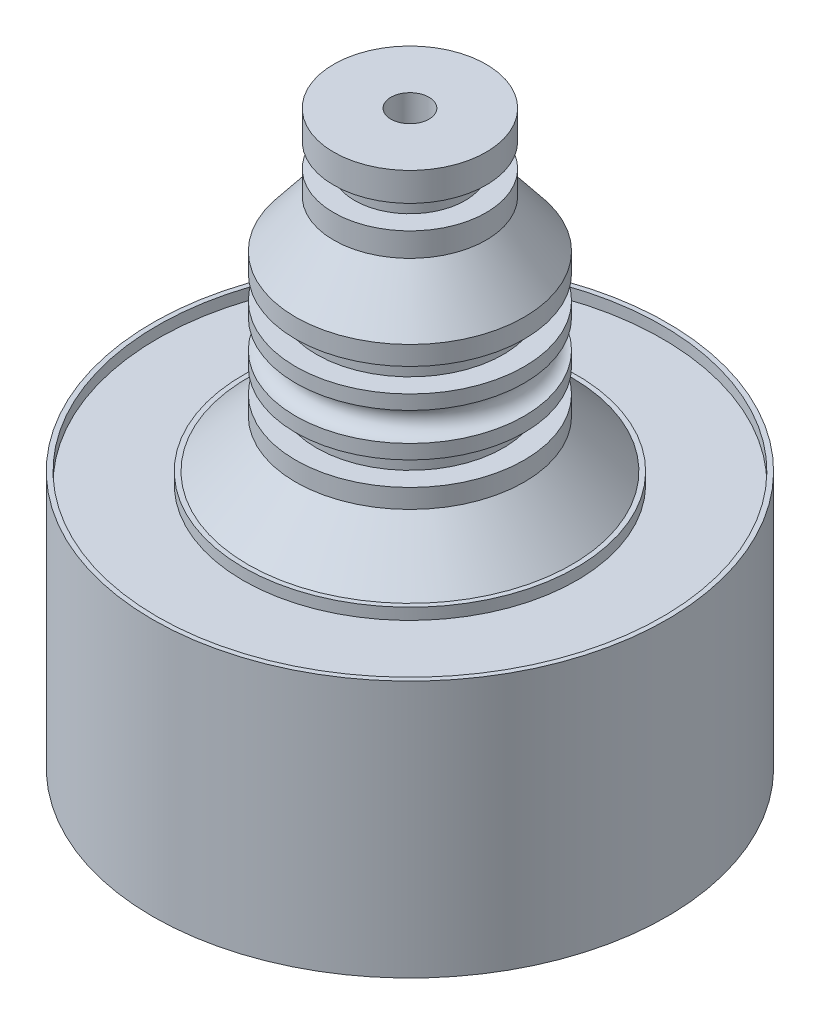
SolidWorks part; units mm, degrees
ref_plane "Спереди" through (0, 0, 0) normal (0, 0, 1) x (1, 0, 0)
ref_plane "Сверху" through (0, 0, 0) normal (0, 1, 0) x (1, 0, 0)
ref_plane "Справа" through (0, 0, 0) normal (1, 0, 0) x (0, 0, -1)
sketch "Эскиз1" plane through (0, 0, 0) normal (0, 0, 1) x (1, 0, 0)
  line L0 (0, 0) -> (0, 60) construction
  line L1 (-25, 0) -> (25, 0) construction
  line L2 (2, 60) -> (2, 0)
  line L4 (2, 60) -> (8, 60)
  line L5 (2, 0) -> (25, 0)
  line L6 (8, 57) -> (5.8, 57)
  line L7 (5.8, 57) -> (5.8, 54.5)
  line L8 (5.8, 54.5) -> (8, 54.5)
  line L10 (8, 60) -> (8, 57)
  line L11 (8, 54.5) -> (8, 52)
  line L12 (8, 52) -> (12, 47)
  line L13 (12, 47) -> (12, 45)
  line L14 (12, 45) -> (9.8, 45)
  line L15 (9.8, 45) -> (9.8, 42.5)
  line L16 (9.8, 42.5) -> (12, 42.5)
  line L17 (12, 39.5) -> (9.0242, 39.5) construction
  line L18 (12, 42.5) -> (12, 41)
  line L19 (12, 36.5) -> (12, 38)
  line L20 (12, 34) -> (9.8, 34)
  line L21 (9.8, 34) -> (9.8, 36.5)
  line L22 (9.8, 36.5) -> (12, 36.5)
  line L23 (12, 34) -> (12, 32)
  line L24 (12, 32) -> (17, 27)
  line L25 (17, 27) -> (17.5, 27)
  line L26 (27, 27) -> (27, 0)
  line L27 (26.5, 27) -> (27, 27)
  line L28 (17.5, 27) -> (17.5, 25.8)
  line L29 (17.5, 25.8) -> (26.5, 25.8)
  line L30 (26.5, 25.8) -> (26.5, 27)
  line L31 (27, 0) -> (25, 0)
  arc A1 (12, 41) -> (12, 38) centre (12, 39.5) ccw
  point P6 (0, 0)
  point P22 (12, 41)
  dimension "D5" = 2.5
  dimension "D14" = 3
  dimension "D1" = 60
  dimension "D2" = 50
  dimension "D3" = 4
  dimension "D4" = 16
  dimension "D6" = 8
  dimension "D7" = 2.2
  dimension "D8" = 3
  dimension "D9" = 24
  dimension "D10" = 5
  dimension "D11" = 2.5
  dimension "D12" = 2.2
  dimension "D13" = 2
  dimension "D15" = 1.5
  dimension "D16" = 2
  dimension "D17" = 5
  dimension "D18" = 34
  dimension "D19" = 0.5
  dimension "D20" = 9
  dimension "D21" = 0.5
  dimension "D22" = 1.2
revolve "Повернуть1" add sketch "Эскиз1" angle 360 about L0 reverse direction yes
